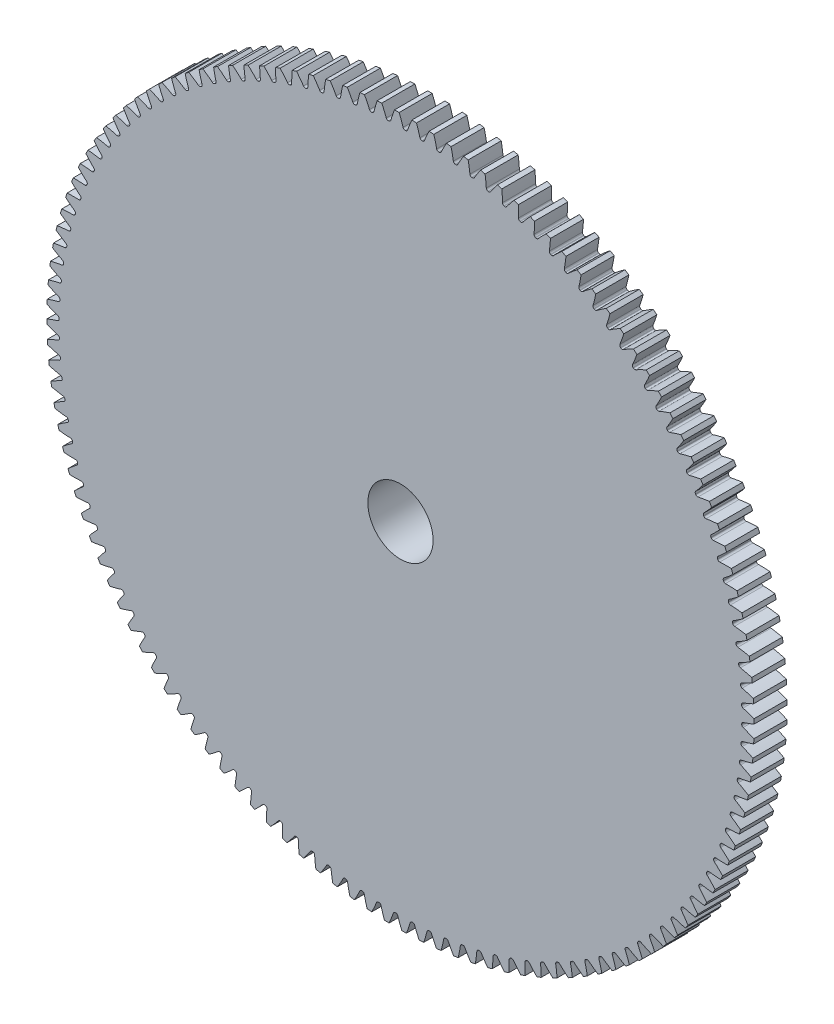
SolidWorks part; units mm, degrees
ref_plane "Front" through (0, 0, 0) normal (0, 0, 1) x (1, 0, 0)
ref_plane "Top" through (0, 0, 0) normal (0, 1, 0) x (1, 0, 0)
ref_plane "Right" through (0, 0, 0) normal (1, 0, 0) x (0, 0, -1)
sketch "Sketch3" plane through (0, 0, 0) normal (0, 0, 1) x (1, 0, 0)
  circle A0 centre (0, 0) radius 51.5938
  dimension "od" = 103.1875
extrude "gearBody" add sketch "Sketch3" along normal blind 4.826
sketch "Sketch2" plane through (0, 0, 0) normal (0, 0, 1) x (1, 0, 0)
  line L0 (0, 0) -> (44.1027, 18.2679) construction
  line L1 (60.0354, -8.954) -> (0, 0) construction
  line L2 (0, 0) -> (36.3143, 0) construction
  line L3 (50.7999, -0.1147) -> (50.7826, -1.3294) construction
  line L5 (50.7912, -0.722) -> (0, 0) construction
  line L7 (0, 0) -> (47.7364, 0) construction
  arc A0 (47.7268, -0.958) -> (47.7347, -0.399) centre (0, 0) ccw construction
  arc A1 (51.5934, 0.1942) -> (51.567, -1.6607) centre (0, 0) ccw construction
  arc A2 (50.7999, -0.1147) -> (50.7826, -1.3294) centre (0, 0) ccw construction
  arc A3 (49.7911, -0.7449) -> (49.7922, -0.6708) centre (0, 0) ccw
  arc A4 (60.0354, -8.954) -> (49.995, -1.0362) centre (43.5656, -19.5142) ccw
  arc A5 (60.0354, -8.954) -> (60.2656, 7.2438) centre (0, 0) ccw
  arc A6 (60.2656, 7.2438) -> (50.0042, -0.3853) centre (44.1027, 18.2679) cw
  arc A7 (49.7922, -0.6708) -> (50.0042, -0.3853) centre (50.0958, -0.6749) cw
  arc A8 (49.995, -1.0362) -> (49.7911, -0.7449) centre (50.0948, -0.7494) cw
  point P6 (60.2656, 7.2438)
  point P22 (60.0354, -8.954)
  dimension "baseDia" = 95.4728
  dimension "od" = 103.1875
  dimension "pd" = 101.6
  dimension "rd" = 99.5934
  dimension "rFillet" = 0.3037
  dimension "pointX" = 60.2656
  dimension "pointY" = 7.2438
  dimension "CTT" = 1.2148
  dimension "flankCenterAngle" = 22.5
extrude "toothCut" cut sketch "Sketch2" along normal through all
pattern_circular "CirPattern1" count 128 over 360 about axis through (0, 0, 0) along (0, 0, 1) of "toothCut"
sketch "hub1Dia" plane through (0, 0, 0) normal (0, 0, -1) x (-1, 0, 0)
  circle A0 centre (0, 0) radius 23.876
  dimension "hub1Dia" = 47.752
extrude "hub1" add sketch "hub1Dia" along normal blind 12.7
sketch "hub2Dia" plane through (0, 0, 4.826) normal (0, 0, 1) x (1, 0, 0)
  circle A0 centre (0, 0) radius 12.7
  dimension "hub2dia" = 25.4
sketch "boreDia" plane through (0, 0, 0) normal (0, 0, 1) x (1, 0, 0)
  circle A0 centre (0, 0) radius 4.7625
  dimension "boreDia" = 9.525
extrude "bore" cut sketch "boreDia" against normal mid plane 25400
